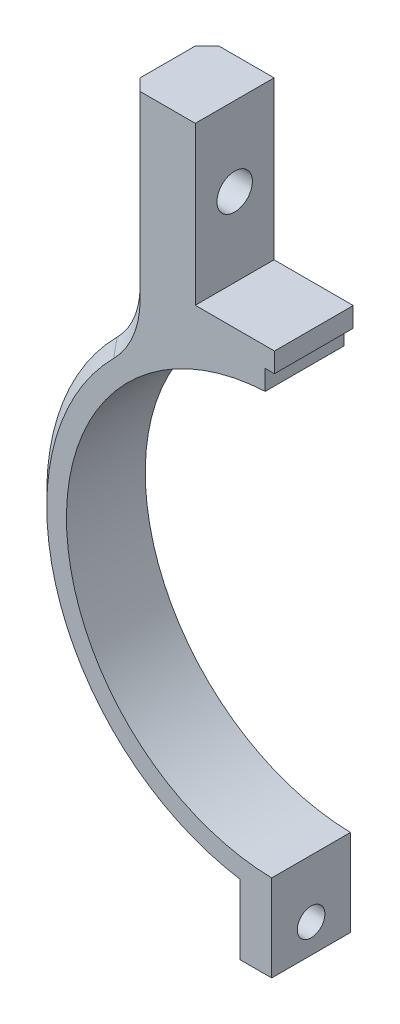
SolidWorks part; units mm, degrees
ref_plane "Ebene vorne" through (0, 0, 0) normal (0, 0, 1) x (1, 0, 0)
ref_plane "Ebene oben" through (0, 0, 0) normal (0, 1, 0) x (1, 0, 0)
ref_plane "Ebene rechts" through (0, 0, 0) normal (1, 0, 0) x (0, 0, -1)
sketch "Skizze1" plane through (0, 0, 0) normal (0, 0, 1) x (1, 0, 0)
  line L0 (0, 0) -> (0, 53.7291) construction
  line L14 (0, 0) -> (0, -44.1347) construction
  line L15 (0.5, -26.5453) -> (0.5, -30.5459)
  line L16 (-0.5, -26.5453) -> (-0.5, -30.5459)
  line L17 (0.5, -30.5459) -> (0.5, -37.5459)
  line L18 (0.5, -37.5459) -> (4.5, -37.5459)
  line L19 (4.5, -37.5459) -> (4.5, -30.2168)
  line L20 (-4.5, -37.5459) -> (-4.5, -30.2168)
  line L21 (-0.5, -37.5459) -> (-4.5, -37.5459)
  line L22 (-0.5, -30.5459) -> (-0.5, -37.5459)
  line L23 (-10.2, 31.55) -> (-10.2, 51.55)
  line L24 (-10.2, 51.55) -> (-18.7, 51.55)
  line L25 (-18.7, 51.55) -> (-18.7, 24.1581)
  line L26 (-10.2, 31.55) -> (10.2, 31.55)
  line L27 (0, 26.55) -> (12.0002, 26.55) construction
  line L28 (18.7, 51.55) -> (18.7, 24.1581)
  line L29 (10.2, 51.55) -> (18.7, 51.55)
  line L30 (10.2, 31.55) -> (10.2, 51.55)
  arc A0 (0.5, -26.5453) -> (-0.5, -26.5453) centre (0, 0) ccw
  arc A1 (-18.7, 24.1581) -> (-4.5, -30.2168) centre (0, 0) ccw
  arc A2 (4.5, -30.2168) -> (18.7, 24.1581) centre (0, 0) ccw
  point P10 (0, 33.5025)
  point P11 (0, 31.6594)
  point P17 (0, 31.55)
  point P18 (0, 39.6025)
  dimension "D1" = 53.1
  dimension "D2" = 4
  dimension "D3" = 20.4
  dimension "D4" = 20
  dimension "D5" = 5
  dimension "D6" = 8.5
  dimension "D10" = 1
  dimension "D11" = 4
  dimension "D12" = 7
extrude "Aufsatz-Linear austragen1" add sketch "Skizze1" along normal blind 10
sketch "Skizze2" plane through (-4.5, 0, 0) normal (-1, 0, 0) x (0, 0, 1)
  line L0 (0, -33.8813) -> (10, -33.8813) construction
  line L1 (0, -30.2168) -> (0, -37.5459) construction
  line L2 (10, -30.2168) -> (10, -37.5459) construction
  circle A0 centre (5, -33.8813) radius 1.75
  dimension "D1" = 3.5
extrude "Schnitt-Linear austragen1" cut sketch "Skizze2" against normal through all
sketch "Skizze3" plane through (0, 0, 10) normal (0, 0, 1) x (1, 0, 0)
  line L0 (-10.8174, 36.4205) -> (0, 26.8755)
  line L1 (0, 26.8755) -> (11.8484, 37.1414)
  line L2 (11.8484, 37.1414) -> (47.3746, 17.8863)
  line L3 (47.3746, 17.8863) -> (51.4546, -59.0738)
  line L4 (51.4546, -59.0738) -> (-81.1349, -43.2704)
  line L5 (-81.1349, -43.2704) -> (-40.9452, 68.8874)
  line L6 (-40.9452, 68.8874) -> (-10.8174, 36.4205)
extrude "Schnitt-Linear austragen2" [suppressed] cut sketch "Skizze3" against normal through all
sketch "Skizze4" plane through (-18.7, 0, 0) normal (-1, 0, 0) x (0, 0, 1)
  line L0 (5, 51.55) -> (5, 31.55) construction
  line L1 (10, 51.55) -> (0, 51.55) construction
  line L3 (10, 31.55) -> (0, 31.55) construction
  circle A0 centre (5, 41.55) radius 2.25
  dimension "D1" = 4.5
extrude "Schnitt-Linear austragen3" cut sketch "Skizze4" against normal through all
fillet "Verrundung1" radius 10 2 edges at (18.7, 24.1581, 5) (-18.7, 24.1581, 5)
sketch "Skizze5" plane through (-4.5, 0, 0) normal (-1, 0, 0) x (0, 0, 1)
  line L0 (5, -33.8813) -> (5, -27.6721) construction
  line L2 (2.225, -36.6563) -> (7.775, -36.6563)
  line L3 (2.225, -36.6563) -> (2.225, -31.1063)
  line L4 (2.225, -31.1063) -> (7.775, -31.1063)
  line L5 (7.775, -36.6563) -> (7.775, -31.1063)
  line L6 (2.225, -36.6563) -> (7.775, -31.1063) construction
  line L7 (2.225, -31.1063) -> (7.775, -36.6563) construction
  dimension "D1" = 5.55
extrude "Schnitt-Linear austragen4" [suppressed] cut sketch "Skizze5" against normal blind 2
sketch "Skizze6" plane through (0, 0, 0) normal (0, 0, 1) x (1, 0, 0)
  line L0 (0, 0) -> (0, 63.9135)
  line L1 (0, 63.9135) -> (40.0139, 63.9135)
  line L2 (40.0139, 63.9135) -> (48.3604, -54.8191)
  line L3 (48.3604, -54.8191) -> (0, -54.8191)
  line L4 (0, -54.8191) -> (0, 0)
extrude "Schnitt-Linear austragen5" cut sketch "Skizze6" along normal through all
chamfer "Fase1" distance 1.5 angle 45 6 edges at (-18.7, 40.0982, 10) (-19.4594, 24.8238, 10) (-29.0064, -9.5882, 10) (-18.7, 40.0982, 0) (-19.4594, 24.8238, 0) (-29.0064, -9.5882, 0)
sketch "Skizze7" plane through (0, 0, 10) normal (0, 0, 1) x (1, 0, 0)
  line L0 (0, 0) -> (0, 40.9199) construction
  line L1 (1.325, 29.05) -> (0, 29.05)
  line L2 (-1.325, 29.05) -> (-1.325, 25.1371)
  line L3 (-1.325, 25.1371) -> (1.325, 25.1371)
  line L4 (0, 26.55) -> (2.8167, 26.55) construction
  line L5 (1.325, 29.05) -> (1.325, 25.1371)
  line L6 (-0.15, 29.05) -> (-0.15, 31.55)
  line L7 (0, 31.55) -> (-10.2, 31.55) construction
  line L8 (-0.15, 31.55) -> (0, 31.55)
  line L9 (0, 31.55) -> (0, 29.05)
  line L10 (-0.15, 29.05) -> (-1.325, 29.05)
  point P11 (0, 25.1371)
  point P12 (0, 29.05)
  dimension "D1" = 2.5
  dimension "D2" = 2.65
  dimension "D3" = 0.15
extrude "Schnitt-Linear austragen6" cut sketch "Skizze7" against normal through all
